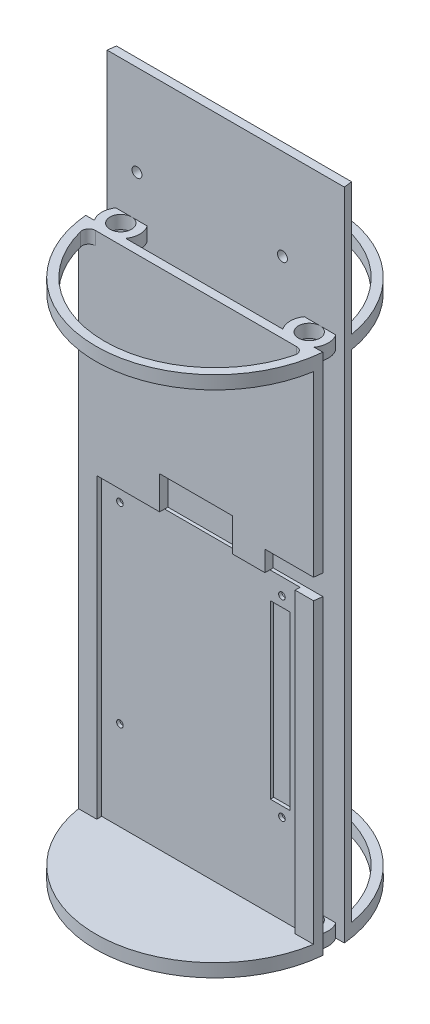
SolidWorks part; units mm, degrees
ref_plane "Front Plane" through (0, 0, 0) normal (0, 0, 1) x (1, 0, 0)
ref_plane "Top Plane" through (0, 0, 0) normal (0, 1, 0) x (1, 0, 0)
ref_plane "Right Plane" through (0, 0, 0) normal (1, 0, 0) x (0, 0, -1)
sketch "Sketch1" plane through (0, 0, 0) normal (0, 1, 0) x (1, 0, 0)
  circle A0 centre (0, 0) radius 36
  dimension "D1" = 72
extrude "Boss-Extrude1" add sketch "Sketch1" along normal blind 4
sketch "Sketch2" plane through (0, 4, 0) normal (0, 1, 0) x (1, 0, 0)
  line L0 (-36.3097, 0) -> (36, 0) construction
  line L1 (35.5378, -5.75) -> (-35.5378, -5.75)
  line L2 (35.5378, -5.75) -> (35.5378, 5.75)
  line L3 (35.5378, 5.75) -> (-35.5378, 5.75)
  line L4 (-35.5378, -5.75) -> (-35.5378, 5.75)
  line L5 (35.5378, -5.75) -> (-35.5378, 5.75) construction
  line L6 (35.5378, 5.75) -> (-35.5378, -5.75) construction
  line L7 (35.853, -3.25) -> (-35.853, -3.25)
  line L8 (35.853, -3.25) -> (35.853, 3.25)
  line L9 (35.853, 3.25) -> (-35.853, 3.25)
  line L10 (-35.853, -3.25) -> (-35.853, 3.25)
  line L11 (35.853, -3.25) -> (-35.853, 3.25) construction
  line L12 (35.853, 3.25) -> (-35.853, -3.25) construction
  circle A0 centre (-28.5, 0) radius 3.25
  circle A1 centre (0, 0) radius 36
  circle A2 centre (0, 0) radius 36
  circle A3 centre (28.5, 0) radius 3.25
  circle A4 centre (-28.5, 0) radius 5.75
  circle A5 centre (28.5, 0) radius 5.75
  circle M4 centre (0, 0) radius 36
  dimension "D5" = 28.5
  dimension "D2" = 11.5
  dimension "D3" = 6.5
  dimension "D4" = 57
  dimension "D1" = 0
extrude "Boss-Extrude2" add sketch "Sketch2" along normal blind 90 contours L9 A4 | A4 L3 L4 L9 | A5 L3 A4 L9 | L9 A5 | A5 L9 L2 L3 | A5 L1 L2 L7 | A5 L7 | A5 L7 A4 L1 | A4 L7 | A4 L7 L4 L1 | L9 L4 M4 | L4 L7 M4 | L9 L2 M4 | L7 L2 M4 region at (33.5238, 4, 4.7055) region at (35.6482, 4, 4.1192) region at (0, 4, 4.5303) region at (28.5, 4, 4.2713) region at (-33.5238, 4, 4.7055) region at (-35.6482, 4, 4.1192) region at (-28.5, 4, 4.2713) region at (33.5238, 4, -4.7055) region at (35.6482, 4, -4.1192) region at (28.5, 4, -4.2713) region at (0, 4, -4.5303) region at (-35.6482, 4, -4.1192) region at (-33.5238, 4, -4.7055) region at (-28.5, 4, -4.2713)
sketch "Sketch4" plane through (0, 4, 0) normal (0, 1, 0) x (1, 0, 0)
  circle A0 centre (-28.5, 0) radius 3.25
  circle A1 centre (28.5, 0) radius 3.25
  dimension "D1" = 6.5
  dimension "D2" = 6.5
  dimension "D3" = 57
  dimension "D4" = 28.5
extrude "Cut-Extrude2" cut sketch "Sketch4" against normal blind 10
sketch "Sketch3" plane through (0, 94, 0) normal (0, 1, 0) x (1, 0, 0)
  line L0 (35.5378, -5.75) -> (-35.5378, -5.75) construction
  line L1 (-30, -5.75) -> (30, -5.75)
  line L2 (-30, -5.75) -> (-30, -4.25)
  line L3 (-30, -4.25) -> (30, -4.25)
  line L4 (30, -5.75) -> (30, -4.25)
  point P6 (-30, -5)
  dimension "D1" = 1.5
  dimension "D2" = 30
  dimension "D3" = 60
extrude "Cut-Extrude1" cut sketch "Sketch3" against normal blind 90
sketch "Sketch6" plane through (0, 0, 4.25) normal (0, 0, 1) x (1, 0, 0)
  line L0 (30, 4) -> (30, 94) construction
  line L1 (27, 86) -> (21, 86)
  line L2 (27, 86) -> (27, 34)
  line L3 (27, 34) -> (21, 34)
  line L4 (21, 86) -> (21, 34)
  line L5 (30, 94) -> (-30, 94) construction
  dimension "D1" = 6
  dimension "D2" = 3
  dimension "D3" = 8
  dimension "D4" = 52
extrude "Cut-Extrude4" cut sketch "Sketch6" against normal blind 5
sketch "Sketch7" plane through (0, 0, 4.25) normal (0, 0, 1) x (1, 0, 0)
  line L0 (30, 94) -> (-30, 94) construction
  line L1 (-30, 4) -> (-30, 94) construction
  circle A0 centre (-24.5, 89) radius 1
  circle A1 centre (24.5, 89) radius 1
  circle A2 centre (24.5, 31) radius 1
  circle A3 centre (-24.5, 31) radius 1
  dimension "D1" = 2
  dimension "D2" = 5
  dimension "D5" = 5.5
  dimension "D3" = 2
  dimension "D4" = 2
extrude "Cut-Extrude5" cut sketch "Sketch7" against normal blind 5 contours A1 | A2 | A3 | A0 region at (24.5, 89, 4.25) region at (24.5, 31, 4.25) region at (-24.5, 31, 4.25)
sketch "Sketch9" plane through (0, 94, 0) normal (0, 1, 0) x (1, 0, 0)
  line L0 (35.853, 3.25) -> (-35.853, 3.25) construction
  line L1 (-28.5, 3.25) -> (-35.853, 3.25) construction
  line L2 (35.5378, 5.75) -> (-35.5378, 5.75) construction
  line L3 (35.853, 3.25) -> (-35.853, 3.25)
  line L4 (-28.5, 3.25) -> (-35.853, 3.25)
  line L5 (35.5378, 5.75) -> (-35.5378, 5.75)
  line L6 (-30, -5.75) -> (-30, -4.25)
  line L7 (-30, -4.25) -> (30, -4.25)
  line L8 (30, -4.25) -> (30, -5.75)
  line L9 (30, -5.75) -> (35.5378, -5.75)
  line L10 (35.853, -3.25) -> (-35.853, -3.25)
  line L11 (-35.5378, -5.75) -> (-30, -5.75)
  line L15 (30, -5.75) -> (35.5378, -5.75)
  line L16 (35.853, -3.25) -> (-35.853, -3.25)
  line L17 (-35.5378, -5.75) -> (-30, -5.75)
  line L18 (-30, -5.75) -> (30, -5.75)
  arc A0 (-35.5378, 5.75) -> (-35.853, 3.25) centre (0, 0) ccw construction
  arc A1 (35.853, 3.25) -> (35.5378, 5.75) centre (0, 0) ccw construction
  arc A2 (35.5378, -5.75) -> (35.853, -3.25) centre (0, 0) ccw
  arc A3 (-35.853, -3.25) -> (-35.5378, -5.75) centre (0, 0) ccw
  arc A4 (35.5378, -5.75) -> (35.853, -3.25) centre (0, 0) ccw
  arc A5 (-35.853, -3.25) -> (-35.5378, -5.75) centre (0, 0) ccw
  arc A6 (-35.5378, 5.75) -> (-35.853, 3.25) centre (0, 0) ccw
  arc A7 (35.853, 3.25) -> (35.5378, 5.75) centre (0, 0) ccw
  line M9 (-30, -5.75) -> (-30, -4.25)
  line M10 (-30, -4.25) -> (30, -4.25)
  line M11 (30, -4.25) -> (30, -5.75)
  line M12 (30, -5.75) -> (35.5378, -5.75)
  arc M13 (35.5378, -5.75) -> (35.853, -3.25) centre (0, 0) ccw
  line M14 (35.853, -3.25) -> (-35.853, -3.25)
  arc M15 (-35.853, -3.25) -> (-35.5378, -5.75) centre (0, 0) ccw
  line M16 (-35.5378, -5.75) -> (-30, -5.75)
  dimension "D1" = 0
extrude "Boss-Extrude3" add sketch "Sketch9" along normal blind 60 contours L3 A7 L5 A6 | M16 M9 M10 M11 M12 M13 M14 M15 | L18 M9 M11 M10 region at (0, 94, -4.4982) region at (0, 94, 3.9881) region at (0, 94, 5)
sketch "Sketch10" plane through (0, 0, 5.75) normal (0, 0, 1) x (1, 0, 0)
  line L0 (30, 94) -> (-30, 94) construction
  line L1 (11, 94) -> (-11, 94)
  line L2 (11, 94) -> (11, 104)
  line L3 (11, 104) -> (-11, 104)
  line L4 (-11, 94) -> (-11, 104)
  line L5 (11, 94) -> (-11, 104) construction
  line L6 (11, 104) -> (-11, 94) construction
  point P4 (0, 99)
  point P7 (0, 0)
  point P9 (4.5378, 99)
  point P10 (4.5378, 99)
  point P11 (4.5378, 99)
  point P12 (0, 0)
  dimension "D1" = 22
  dimension "D2" = 10
extrude "Cut-Extrude6" cut sketch "Sketch10" against normal blind 5 contours L4 L3 L2 L1
sketch "Sketch11" plane through (0, 154, 0) normal (0, 1, 0) x (1, 0, 0)
  line L5 (-35.5378, -5.75) -> (35.5378, -5.75) construction
  line L6 (-23.7566, 3.25) -> (23.7566, 3.25)
  line L7 (35.853, 3.25) -> (28.5, 3.25) construction
  line L8 (35.5378, 5.75) -> (-35.5378, 5.75) construction
  line L9 (35.853, -3.25) -> (-35.853, -3.25) construction
  line L10 (-28.5, 3.25) -> (-35.853, 3.25) construction
  line L11 (-35.853, -3.25) -> (-28.5, -3.25) construction
  line L12 (-35.853, 3.25) -> (35.853, 3.25) construction
  line L13 (-30.4305, -5.75) -> (30.4305, -5.75)
  line L14 (-28.5, -3.25) -> (28.5, -3.25) construction
  line L15 (28.5, 3.25) -> (-28.5, 3.25) construction
  line L18 (-33.2434, -3.25) -> (-35.853, -3.25)
  line L21 (30.4305, 5.75) -> (-30.4305, 5.75)
  line L23 (35.853, 3.25) -> (33.2434, 3.25)
  line L25 (35.853, -3.25) -> (28.5, -3.25)
  line L26 (-33.2434, 3.25) -> (-35.853, 3.25)
  line L27 (-35.853, -3.25) -> (-33.2434, -3.25)
  line L28 (-35.853, 3.25) -> (28.5, 3.25)
  line L30 (-23.7566, -3.25) -> (23.7566, -3.25)
  line L31 (28.5, 3.25) -> (-28.5, 3.25)
  line L32 (23.7566, -3.25) -> (-23.7566, -3.25)
  line L33 (33.2434, 3.25) -> (35.853, 3.25)
  arc A0 (-35.5378, -5.75) -> (35.5378, -5.75) centre (0, 0) ccw construction
  arc A1 (35.5378, 5.75) -> (-35.5378, 5.75) centre (0, 0) ccw construction
  arc A2 (28.5, -3.25) -> (28.5, 3.25) centre (28.5, 0) ccw construction
  arc A3 (35.853, -3.25) -> (35.853, 3.25) centre (0, 0) ccw construction
  arc A4 (35.5378, -5.75) -> (35.853, -3.25) centre (0, 0) ccw construction
  arc A5 (-35.853, -3.25) -> (-35.5378, -5.75) centre (0, 0) ccw construction
  arc A6 (-28.5, 3.25) -> (-28.5, -3.25) centre (-28.5, 0) ccw construction
  arc A7 (-35.853, 3.25) -> (-35.853, -3.25) centre (0, 0) ccw construction
  arc A8 (35.853, 3.25) -> (35.5378, 5.75) centre (0, 0) ccw construction
  arc A9 (-35.5378, 5.75) -> (-35.853, 3.25) centre (0, 0) ccw construction
  arc A10 (-28.5, -3.25) -> (-28.5, 3.25) centre (-28.5, 0) ccw construction
  arc A11 (28.5, 3.25) -> (28.5, -3.25) centre (28.5, 0) ccw construction
  arc A12 (-35.5378, -5.75) -> (35.5378, -5.75) centre (0, 0) ccw
  arc A13 (35.5378, 5.75) -> (-35.5378, 5.75) centre (0, 0) ccw
  arc A14 (28.5, -3.25) -> (28.5, 3.25) centre (28.5, 0) ccw
  arc A15 (35.853, -3.25) -> (35.853, 3.25) centre (0, 0) ccw
  arc A16 (35.5378, -5.75) -> (35.853, -3.25) centre (0, 0) ccw
  arc A17 (-35.853, -3.25) -> (-35.5378, -5.75) centre (0, 0) ccw
  arc A18 (-28.5, 3.25) -> (-28.5, -3.25) centre (-28.5, 0) ccw
  arc A19 (-35.853, 3.25) -> (-35.853, -3.25) centre (0, 0) ccw
  arc A20 (35.853, 3.25) -> (35.5378, 5.75) centre (0, 0) ccw
  arc A21 (-35.5378, 5.75) -> (-35.853, 3.25) centre (0, 0) ccw
  arc A22 (-28.5, -3.25) -> (-28.5, 3.25) centre (-28.5, 0) ccw
  arc A23 (28.5, 3.25) -> (28.5, -3.25) centre (28.5, 0) ccw
  arc A24 (-33.2434, 3.25) -> (-33.2434, -3.25) centre (-28.5, 0) ccw
  arc A25 (23.7566, 3.25) -> (23.7566, -3.25) centre (28.5, 0) ccw
  arc A28 (-23.7566, -3.25) -> (-23.7566, 3.25) centre (-28.5, 0) ccw
  arc A29 (-32.3687, -8.2436) -> (32.3687, -8.2436) centre (0, 0) ccw
  arc A30 (33.2434, -3.25) -> (33.2434, 3.25) centre (28.5, 0) ccw
  arc A32 (32.3687, 8.2436) -> (-32.3687, 8.2436) centre (0, 0) ccw
  arc A33 (30.4305, -5.75) -> (32.3687, -8.2436) centre (30.4305, -7.75) cw
  arc A34 (-30.4305, -5.75) -> (-32.3687, -8.2436) centre (-30.4305, -7.75) ccw
  arc A35 (-32.3687, 8.2436) -> (-30.4305, 5.75) centre (-30.4305, 7.75) ccw
  arc A36 (32.3687, 8.2436) -> (30.4305, 5.75) centre (30.4305, 7.75) cw
  line M1 (-35.853, 3.25) -> (35.853, 3.25)
  arc M2 (35.853, 3.25) -> (35.5378, 5.75) centre (0, 0) ccw
  line M3 (35.5378, 5.75) -> (-35.5378, 5.75)
  arc M4 (-35.5378, 5.75) -> (-35.853, 3.25) centre (0, 0) ccw
  dimension "D1" = 2
  dimension "D2" = 2
  dimension "D3" = 2
extrude "Boss-Extrude4" add sketch "Sketch11" along normal blind 4 contours L28 M4 M1 M2 M3 | A32 A36 A13 A35 M3 | L30 A28 L28 A22 A18 A24 L18 A17 A12 A16 L25 A23 A25 A34 L13 A33 A29 M1 | L25 A30 A14 M1 region at (0, 154, -4.4982) region at (-23.5675, 154, 0) region at (32.4135, 154, 0) region at (0, 154, -35.2275)
sketch "Sketch12" plane through (0, 158, 0) normal (0, 1, 0) x (1, 0, 0)
  line L1 (-35.853, 3.25) -> (35.853, 3.25)
  line L3 (-35.5378, 5.75) -> (35.5378, 5.75)
  arc A0 (35.853, 3.25) -> (-35.853, 3.25) centre (0, 0) ccw construction
  arc A1 (35.853, 3.25) -> (35.5378, 5.75) centre (0, 0) ccw
  arc A2 (-35.5378, 5.75) -> (-35.853, 3.25) centre (0, 0) ccw
extrude "Boss-Extrude5" add sketch "Sketch12" along normal blind 40
sketch "Sketch13" plane through (0, 0, 5.75) normal (0, 0, 1) x (1, 0, 0)
  line L0 (35.853, 158) -> (35.853, 4) construction
  line L1 (35.853, 94) -> (20.853, 94)
  line L2 (35.853, 94) -> (35.853, 100.1572)
  line L3 (35.853, 100.1572) -> (20.853, 100.1572)
  line L4 (20.853, 94) -> (20.853, 100.1572)
  dimension "D1" = 15
extrude "Cut-Extrude8" cut sketch "Sketch13" against normal blind 4
sketch "Sketch14" plane through (0, 0, 0) normal (0, -1, 0) x (1, 0, 0)
  line L0 (-28.5, 3.25) -> (-33.2434, 3.25) construction
  line L1 (-33.2434, -3.25) -> (-28.5, -3.25) construction
  line L2 (-23.7566, 3.25) -> (-28.5, 3.25) construction
  line L3 (-28.5, -3.25) -> (-23.7566, -3.25) construction
  line L4 (28.5, 3.25) -> (23.7566, 3.25) construction
  line L5 (23.7566, -3.25) -> (28.5, -3.25) construction
  line L6 (33.2434, 3.25) -> (28.5, 3.25) construction
  line L7 (28.5, -3.25) -> (33.2434, -3.25) construction
  line L8 (35.5378, -5.75) -> (30.4305, -5.75) construction
  line L9 (-30.4305, -5.75) -> (-35.5378, -5.75) construction
  line L10 (30.4305, 5.75) -> (35.5378, 5.75) construction
  line L11 (-35.5378, 5.75) -> (-30.4305, 5.75) construction
  line L12 (-28.5, 3.25) -> (-33.2434, 3.25)
  line L13 (-33.2434, -3.25) -> (-28.5, -3.25)
  line L14 (-23.7566, 3.25) -> (-28.5, 3.25)
  line L15 (-28.5, -3.25) -> (-23.7566, -3.25)
  line L16 (28.5, 3.25) -> (23.7566, 3.25)
  line L17 (23.7566, -3.25) -> (28.5, -3.25)
  line L18 (33.2434, 3.25) -> (28.5, 3.25)
  line L19 (28.5, -3.25) -> (33.2434, -3.25)
  line L20 (35.5378, -5.75) -> (30.4305, -5.75)
  line L21 (-30.4305, -5.75) -> (-35.5378, -5.75)
  line L22 (30.4305, 5.75) -> (35.5378, 5.75)
  line L23 (-35.5378, 5.75) -> (-30.4305, 5.75)
  line L24 (-33.2434, -3.25) -> (-35.853, -3.25)
  line L25 (30.4305, -5.75) -> (-30.4305, -5.75)
  line L26 (30.4305, -5.75) -> (30.4305, 5.75)
  line L27 (30.4305, 5.75) -> (-30.4305, 5.75)
  line L28 (-30.4305, -5.75) -> (-30.4305, 5.75)
  line L29 (-23.7566, 3.25) -> (23.7566, 3.25)
  line L30 (-23.7566, 3.25) -> (-23.7566, -3.25)
  line L31 (-23.7566, -3.25) -> (23.7566, -3.25)
  line L32 (23.7566, 3.25) -> (23.7566, -3.25)
  line L33 (-33.2434, 3.25) -> (-35.853, 3.25)
  line L34 (33.2434, 3.25) -> (35.853, 3.25)
  line L35 (33.2434, -3.25) -> (35.853, -3.25)
  arc A0 (-28.5, 3.25) -> (-28.5, -3.25) centre (-28.5, 0) ccw construction
  arc A1 (-33.2434, 3.25) -> (-33.2434, -3.25) centre (-28.5, 0) ccw construction
  arc A2 (-23.7566, -3.25) -> (-23.7566, 3.25) centre (-28.5, 0) ccw construction
  arc A3 (-28.5, -3.25) -> (-28.5, 3.25) centre (-28.5, 0) ccw construction
  arc A4 (28.5, 3.25) -> (28.5, -3.25) centre (28.5, 0) ccw construction
  arc A5 (23.7566, 3.25) -> (23.7566, -3.25) centre (28.5, 0) ccw construction
  arc A6 (33.2434, -3.25) -> (33.2434, 3.25) centre (28.5, 0) ccw construction
  arc A7 (28.5, -3.25) -> (28.5, 3.25) centre (28.5, 0) ccw construction
  arc A8 (-35.5378, -5.75) -> (35.5378, -5.75) centre (0, 0) ccw construction
  arc A9 (32.3687, -8.2436) -> (30.4305, -5.75) centre (30.4305, -7.75) ccw construction
  arc A10 (-32.3687, -8.2436) -> (32.3687, -8.2436) centre (0, 0) ccw construction
  arc A11 (-30.4305, -5.75) -> (-32.3687, -8.2436) centre (-30.4305, -7.75) ccw construction
  arc A12 (35.5378, 5.75) -> (-35.5378, 5.75) centre (0, 0) ccw construction
  arc A13 (-32.3687, 8.2436) -> (-30.4305, 5.75) centre (-30.4305, 7.75) ccw construction
  arc A14 (32.3687, 8.2436) -> (-32.3687, 8.2436) centre (0, 0) ccw construction
  arc A15 (30.4305, 5.75) -> (32.3687, 8.2436) centre (30.4305, 7.75) ccw construction
  arc A16 (-28.5, 3.25) -> (-28.5, -3.25) centre (-28.5, 0) ccw
  arc A17 (-33.2434, 3.25) -> (-33.2434, -3.25) centre (-28.5, 0) ccw
  arc A18 (-23.7566, -3.25) -> (-23.7566, 3.25) centre (-28.5, 0) ccw
  arc A19 (-28.5, -3.25) -> (-28.5, 3.25) centre (-28.5, 0) ccw
  arc A20 (28.5, 3.25) -> (28.5, -3.25) centre (28.5, 0) ccw
  arc A21 (23.7566, 3.25) -> (23.7566, -3.25) centre (28.5, 0) ccw
  arc A22 (33.2434, -3.25) -> (33.2434, 3.25) centre (28.5, 0) ccw
  arc A23 (28.5, -3.25) -> (28.5, 3.25) centre (28.5, 0) ccw
  arc A24 (-35.5378, -5.75) -> (35.5378, -5.75) centre (0, 0) ccw
  arc A25 (32.3687, -8.2436) -> (30.4305, -5.75) centre (30.4305, -7.75) ccw
  arc A26 (-32.3687, -8.2436) -> (32.3687, -8.2436) centre (0, 0) ccw
  arc A27 (-30.4305, -5.75) -> (-32.3687, -8.2436) centre (-30.4305, -7.75) ccw
  arc A28 (35.5378, 5.75) -> (-35.5378, 5.75) centre (0, 0) ccw
  arc A29 (-32.3687, 8.2436) -> (-30.4305, 5.75) centre (-30.4305, 7.75) ccw
  arc A30 (32.3687, 8.2436) -> (-32.3687, 8.2436) centre (0, 0) ccw
  arc A31 (30.4305, 5.75) -> (32.3687, 8.2436) centre (30.4305, 7.75) ccw
  circle A32 centre (0, 0) radius 36 construction
  circle A34 centre (0, 0) radius 36
  circle A35 centre (0, 0) radius 36
  circle M3 centre (0, 0) radius 36
  dimension "D1" = 0
extrude "Cut-Extrude9" cut sketch "Sketch14" against normal blind 4 contours L25 A27 A26 A25 | A21 L29 A18 L31 | A17 L33 L24 M3 | A22 L35 L34 M3 region at (0, 0, 0) region at (-34.918, 0, 0) region at (0, 0, -17.3533) region at (34.918, 0, 0)
sketch "Sketch8" plane through (0, 0, -5.75) normal (0, 0, -1) x (-1, 0, 0)
  line L0 (35.853, 198) -> (35.853, 0) construction
  line L1 (-17.147, 82.5) -> (26.853, 82.5)
  line L2 (-17.147, 82.5) -> (-17.147, 170.5)
  line L3 (-17.147, 170.5) -> (26.853, 170.5)
  line L4 (26.853, 82.5) -> (26.853, 170.5)
  line L5 (-17.147, 82.5) -> (26.853, 170.5) construction
  line L6 (-17.147, 170.5) -> (26.853, 82.5) construction
  line L7 (-35.5378, 198) -> (35.5378, 198) construction
  circle A0 centre (-17.147, 170.5) radius 1.5
  circle A1 centre (26.853, 170.5) radius 1.5
  circle A2 centre (26.853, 82.5) radius 1.5
  circle A3 centre (-17.147, 82.5) radius 1.5
  point P3 (4.853, 126.5)
  dimension "D1" = 3
  dimension "D5" = 27.5
  dimension "D4" = 9
  dimension "D2" = 2
  dimension "D3" = 2
extrude "Cut-Extrude7" cut sketch "Sketch8" against normal blind 5 contours A3 | A2 | A1 | A0
